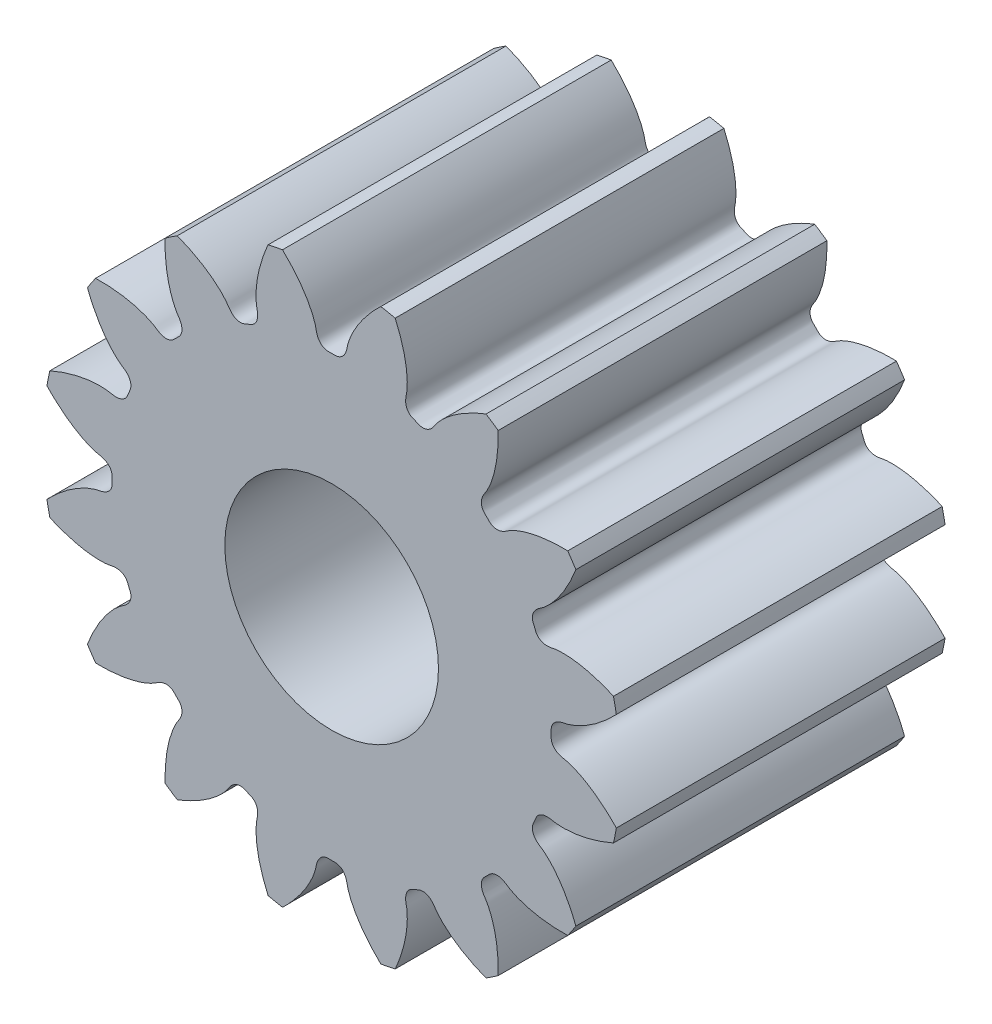
SolidWorks part; units mm, degrees
material "Д16 ГОСТ 4784-97"
ref_plane "FRONT" through (0, 0, 0) normal (0, 0, 1) x (1, 0, 0)
ref_plane "TOP" through (0, 0, 0) normal (0, 1, 0) x (1, 0, 0)
ref_plane "RIGHT" through (0, 0, 0) normal (1, 0, 0) x (0, 0, -1)
ref_axis "Ось1" through (0, 0, 50) along (0, 0, -1)
sketch "SketchRevolveSpurAssemblyNew1Pinion" plane through (0, 0, 0) normal (1, 0, 0) x (0, 0, -1)
  line L0 (0, 0) -> (1, 0) construction
  line L1 (-4, 0) -> (-4, 8.7891)
  line L2 (-4, 8.7891) -> (6, 8.7891)
  line L3 (6, 8.7891) -> (6, 0)
  line L4 (6, 0) -> (-4, 0)
  dimension "D1" = 4
  dimension "D2" = 10
revolve "SpurAssemblyNew1Pinion" add sketch "SketchRevolveSpurAssemblyNew1Pinion" angle 360 about L0
sketch "SketchToothSpurAssemblyNew1Pinion" plane through (0, 0, 0) normal (0, 0, 1) x (1, 0, 0)
  arc A0 (8.716, 1.5542) -> (8.716, -1.5542) centre (0, 0) cw
  spline S0 degree 3 poles (8.716, -1.5542) (8.6286, -1.4593) (8.496, -1.3253) (8.3141, -1.1618) (8.1849, -1.0543) (8.0598, -0.958) (7.9394, -0.8724) (7.8244, -0.797) (7.7153, -0.7313) (7.6127, -0.6747) (7.5171, -0.6266) (7.4291, -0.5864) (7.349, -0.5534) (7.2773, -0.5271) (7.2144, -0.5065) (7.1604, -0.4913) (7.098, -0.4758) (7.0463, -0.4679) (7.0043, -0.4578) (6.9857, -0.4529) (6.9673, -0.4474) (6.9491, -0.4414) (6.9309, -0.4347) (6.9128, -0.4273) (6.8947, -0.4192) (6.8765, -0.4101) (6.8582, -0.3999) (6.8397, -0.3884) (6.821, -0.3754) (6.8021, -0.3606) (6.7831, -0.3437) (6.7641, -0.3241) (6.7455, -0.3015) (6.7276, -0.2756) (6.7111, -0.246) (6.697, -0.2126) (6.6863, -0.1759) (6.68, -0.1381) (6.6779, -0.0791) (6.681, 0) (6.6779, 0.0791) (6.68, 0.1381) (6.6863, 0.1759) (6.697, 0.2126) (6.7111, 0.246) (6.7276, 0.2756) (6.7455, 0.3015) (6.7641, 0.3241) (6.7831, 0.3437) (6.8021, 0.3606) (6.821, 0.3754) (6.8397, 0.3884) (6.8582, 0.3999) (6.8765, 0.4101) (6.8947, 0.4192) (6.9128, 0.4273) (6.9309, 0.4347) (6.9491, 0.4414) (6.9673, 0.4474) (6.9857, 0.4529) (7.0043, 0.4578) (7.0463, 0.4679) (7.098, 0.4758) (7.1604, 0.4913) (7.2144, 0.5065) (7.2773, 0.5271) (7.349, 0.5534) (7.4291, 0.5864) (7.5171, 0.6266) (7.6127, 0.6747) (7.7153, 0.7313) (7.8244, 0.797) (7.9394, 0.8724) (8.0598, 0.958) (8.1849, 1.0543) (8.3141, 1.1618) (8.496, 1.3253) (8.6286, 1.4593) (8.716, 1.5542) knots 0 0 0 0 0.07194 0.10507 0.136308 0.165652 0.193102 0.21866 0.242325 0.264096 0.283974 0.301959 0.318051 0.33225 0.344555 0.354968 0.363487 0.380444 0.384031 0.387599 0.39116 0.394727 0.398315 0.401941 0.405627 0.409398 0.413281 0.41731 0.421523 0.425965 0.430682 0.435726 0.441147 0.446987 0.453273 0.460003 0.467133 0.474573 0.481319 0.5 0.518681 0.525427 0.532867 0.539997 0.546727 0.553013 0.558853 0.564274 0.569318 0.574035 0.578477 0.58269 0.586719 0.590602 0.594373 0.598059 0.601685 0.605273 0.60884 0.612401 0.615969 0.619556 0.636513 0.645032 0.655445 0.66775 0.681949 0.698041 0.716026 0.735904 0.757675 0.78134 0.806898 0.834348 0.863692 0.89493 0.92806 1 1 1 1
extrude "ToothExtrudeCutSpurAssemblyNew1Pinion" cut sketch "SketchToothSpurAssemblyNew1Pinion" against normal blind 8 and the other way blind 4
pattern_circular "PatternSpurAssemblyNew1Pinion" count 16 every 22.5 about axis through (0, 0, 50) along (0, 0, -1) of "ToothExtrudeCutSpurAssemblyNew1Pinion"
sketch "AuxiliarySketchSpurAssemblyNew1Pinion" plane through (0, 0, 0) normal (0, 0, 1) x (1, 0, 0)
  circle A0 centre (0, 0) radius 7.5 construction
  circle A1 centre (0, 0) radius 7.0477 construction
  circle A2 centre (0, 0) radius 7.0831 construction
  circle A3 centre (0, 0) radius 8.7891 construction
  circle A4 centre (0, 0) radius 6.6797 construction
  dimension "PitchDiameter" = 15
  dimension "BaseDiameter" = 14.0954
  dimension "FormDiameter" = 14.1663
  dimension "MajorDiameter" = 17.5781
  dimension "MinorDiameter" = 13.3594
sketch "Эскиз1" plane through (0, 0, 4) normal (0, 0, 1) x (1, 0, 0)
  circle A0 centre (0, 0) radius 3.25
  dimension "D1" = 6.5
extrude "Вырез-Вытянуть1" cut sketch "Эскиз1" against normal through all
